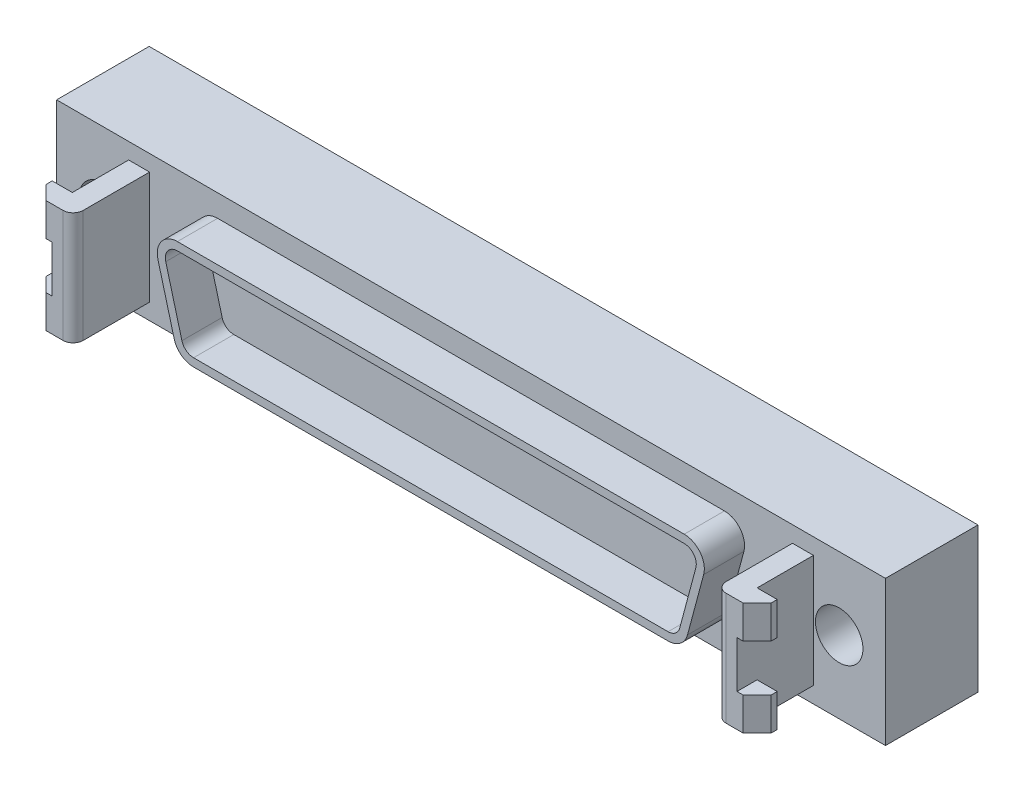
SolidWorks part; units mm, degrees
ref_plane "Front Plane" through (0, 0, 0) normal (0, 0, 1) x (1, 0, 0)
ref_plane "Top Plane" through (0, 0, 0) normal (0, 1, 0) x (1, 0, 0)
ref_plane "Right Plane" through (0, 0, 0) normal (1, 0, 0) x (0, 0, -1)
sketch "Base Outline" plane through (0, 0, 0) normal (0, 0, 1) x (1, 0, 0)
  line L0 (26.162, 0) -> (-26.162, 0) construction
  line L2 (-26.162, 4.572) -> (26.162, 4.572)
  line L3 (-26.162, 4.572) -> (-26.162, -4.572)
  line L4 (-26.162, -4.572) -> (26.162, -4.572)
  line L5 (26.162, 4.572) -> (26.162, -4.572)
  circle A0 centre (-23.241, 0) radius 1.4986
  circle A1 centre (23.241, 0) radius 1.4986
  point P5 (0, 0)
  point P6 (-26.162, 4.572)
  point P8 (26.162, -4.572)
  point P11 (-23.241, 0)
  point P12 (23.241, 0)
  dimension "D6" = 2.9972
  dimension "D7" = 2.9972
  dimension "D1" = 52.324
  dimension "D2" = 4.572
  dimension "D3" = 4.572
  dimension "D4" = 2.921
  dimension "D5" = 2.921
extrude "Connector Base" add sketch "Base Outline" along normal blind 5.842
sketch "Connector Outline" plane through (0, 0, 5.842) normal (0, 0, 1) x (1, 0, 0)
  line L0 (-15.9979, 3.175) -> (15.9979, 3.175)
  line L1 (-17.653, 3.175) -> (-17.653, -2.8641) construction
  line L2 (17.653, 3.175) -> (17.653, -2.8641) construction
  line L3 (-17.2246, 1.5763) -> (-16.2037, -2.2337)
  line L4 (17.2246, 1.5763) -> (16.2037, -2.2337)
  line L5 (14.977, -3.175) -> (-14.977, -3.175)
  arc A0 (-17.2246, 1.5763) -> (-15.9979, 3.175) centre (-15.9979, 1.905) cw
  arc A1 (-14.977, -3.175) -> (-16.2037, -2.2337) centre (-14.977, -1.905) cw
  arc A2 (16.2037, -2.2337) -> (14.977, -3.175) centre (14.977, -1.905) cw
  arc A3 (17.2246, 1.5763) -> (15.9979, 3.175) centre (15.9979, 1.905) ccw
  point P2 (0, 0)
  point P3 (0, 3.175)
  dimension "D6" = 1.27
  dimension "D7" = 1.27
  dimension "D1" = 3.175
  dimension "D2" = 35.306
  dimension "D3" = 3.175
  dimension "D4" = 15
  dimension "D5" = 15
extrude "Connector" add sketch "Connector Outline" along normal blind 2.54 thin thin type one direction reverse wall 0.508
sketch "Clip Outline" plane through (0, 0, 0) normal (0, 1, 0) x (1, 0, 0)
  line L0 (-21.6154, -5.842) -> (-20.2946, -5.842)
  line L1 (26.162, -5.842) -> (-26.162, -5.842) construction
  line L2 (-20.2946, -5.842) -> (-20.2946, -10.033)
  line L3 (-20.9296, -10.668) -> (-22.0069, -10.668)
  line L4 (-22.8854, -9.7895) -> (-22.8854, -9.398)
  line L5 (-22.8854, -9.398) -> (-21.6154, -9.398)
  line L6 (-21.6154, -9.398) -> (-21.6154, -5.842)
  line L7 (-22.0069, -10.668) -> (-22.8854, -9.7895)
  arc A0 (-20.9296, -10.668) -> (-20.2946, -10.033) centre (-20.9296, -10.033) ccw
  point P6 (-21.6154, -5.842)
  point P10 (-22.8854, -9.7895)
  point P11 (-22.0069, -10.668)
  dimension "D5" = 0.635
  dimension "D1" = 1.27
  dimension "D2" = 1.27
  dimension "D3" = 1.3208
  dimension "D4" = 0.127
extrude "Clip" add sketch "Clip Outline" along normal mid plane 7.112
sketch "Cut Outline" plane through (0, 0, 9.398) normal (0, 0, -1) x (-1, 0, 0)
  line L0 (21.6154, 3.556) -> (21.6154, -3.556) construction
  line L1 (21.6154, -1.4732) -> (22.8854, -1.4732)
  line L2 (21.6154, -1.4732) -> (21.6154, 1.4732)
  line L3 (21.6154, 1.4732) -> (22.8854, 1.4732)
  line L4 (22.8854, -1.4732) -> (22.8854, 1.4732)
  line L5 (22.8854, 3.556) -> (22.8854, -3.556) construction
extrude "Clip Cut" cut sketch "Cut Outline" against normal up to next
mirror "Clip Mirror" about plane through (0, 0, 0) normal (1, 0, 0) of "Clip", "Clip Cut"
